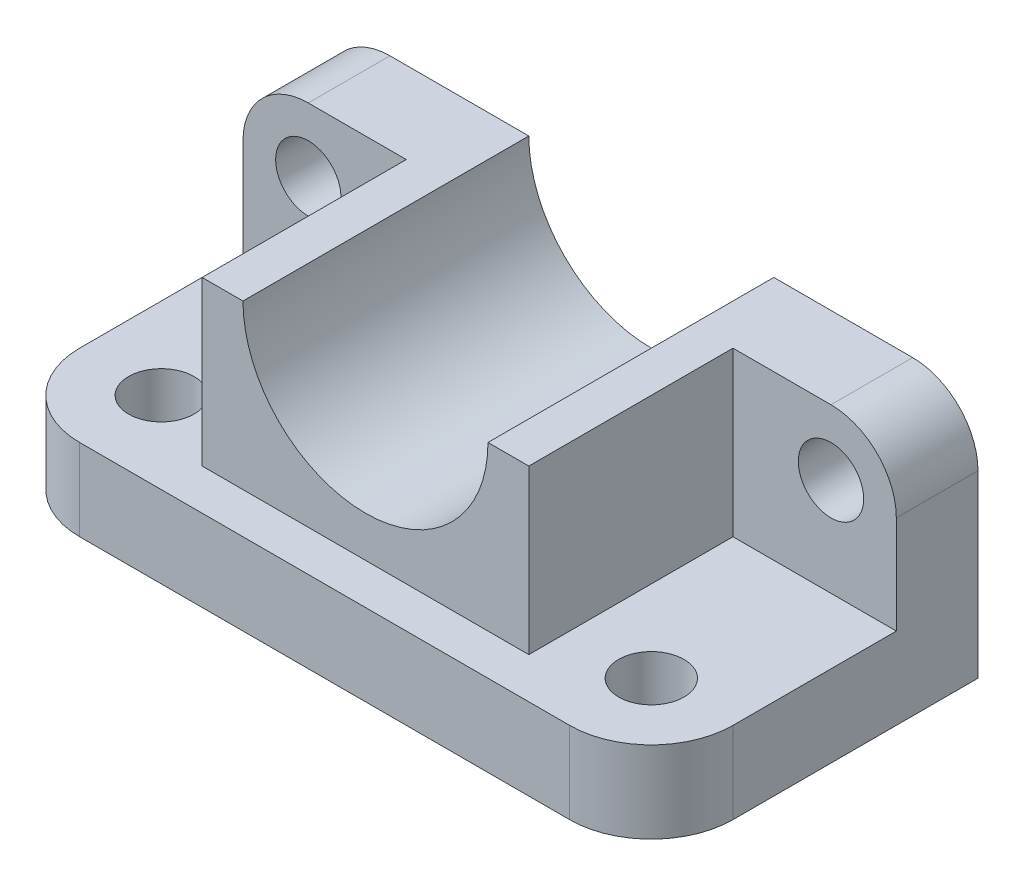
SolidWorks part; units mm, degrees
ref_plane "Front Plane" through (0, 0, 0) normal (0, 0, 1) x (1, 0, 0)
ref_plane "Top Plane" through (0, 0, 0) normal (0, 1, 0) x (1, 0, 0)
ref_plane "Right Plane" through (0, 0, 0) normal (1, 0, 0) x (0, 0, -1)
sketch "Sketch1" plane through (0, 0, 0) normal (0, 1, 0) x (1, 0, 0)
  line L0 (40, 30) -> (20, 30)
  line L1 (0, 0) -> (40, 0)
  line L2 (0, 0) -> (0, 40)
  line L3 (0, 40) -> (40, 40)
  line L4 (40, 0) -> (40, 40)
  line L5 (20, 30) -> (20, 5)
  line L6 (20, 5) -> (0, 5)
  dimension "D1" = 40
  dimension "D2" = 40
  dimension "D3" = 10
  dimension "D4" = 20
  dimension "D5" = 35
extrude "Boss-Extrude1" add sketch "Sketch1" along normal blind 10 contours L5 L6 L2 L1 L4 L0 region at (27.1429, 0, -13.2143)
extrude "Boss-Extrude2" add sketch "Sketch1<3>" along normal blind 30 contours L6 L5 L0 L4 L3 L2 region at (14.4444, 0, -25.2778)
sketch "Sketch1<3>" plane through (0, 0, 0) normal (0, 1, 0) x (1, 0, 0) same geometry as "Sketch1"
sketch "Sketch2" plane through (0, 0, -5) normal (0, 0, 1) x (1, 0, 0)
  line L0 (20, 30) -> (0, 30) construction
  line L1 (0, 30) -> (0, 10) construction
  line L2 (15, 30) -> (0, 30)
  line L3 (0, 30) -> (0, 15)
  arc A0 (15, 30) -> (0, 15) centre (0, 30) cw
  point P3 (13.7049, 33.7808)
  point P6 (18.1641, 30)
  point P8 (0, 12.2716)
  point P9 (2.6397, 27.8614)
  dimension "D1" = 15
extrude "Cut-Extrude1" cut sketch "Sketch2" against normal up to next
sketch "Sketch3" plane through (0, 10, 0) normal (0, 1, 0) x (1, 0, 0)
  line L0 (40, 0) -> (40, 30) construction
  line L1 (0, 0) -> (40, 0) construction
  circle A0 centre (30, 10) radius 4
  dimension "D3" = 8
  dimension "D1" = 10
  dimension "D2" = 10
extrude "Cut-Extrude2" cut sketch "Sketch3" against normal up to next
fillet "Fillet1" radius 10 1 edges at (40, 5, 0)
fillet "Fillet2" radius 8 1 edges at (40, 30, -35)
sketch "Sketch4" plane through (0, 0, -30) normal (0, 0, 1) x (1, 0, 0)
  arc A0 (40, 22) -> (32, 30) centre (32, 22) ccw construction
  arc A1 (40, 22) -> (32, 30) centre (32, 22) ccw
  circle A2 centre (32, 22) radius 4
  dimension "D1" = 8
extrude "Cut-Extrude3" cut sketch "Sketch4" against normal up to next contours A2 region at (32, 22, -30)
mirror "Mirror1" about plane through (0, 10, 0) normal (-1, 0, 0) of bodies 105
